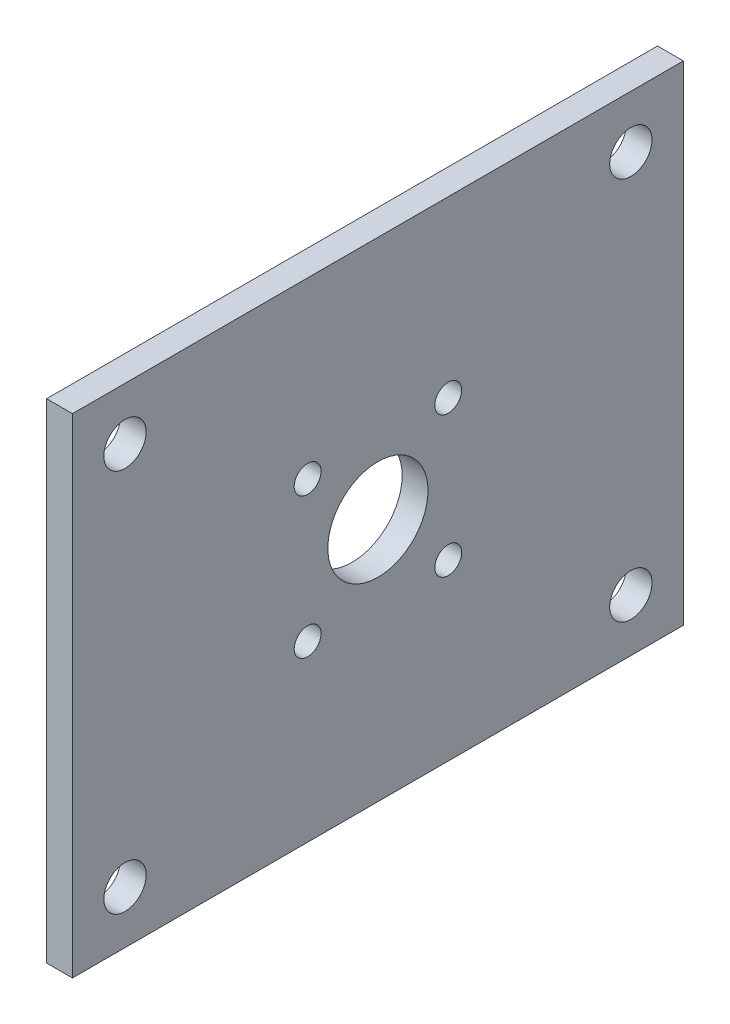
SolidWorks part; units mm, degrees
ref_plane "Front Plane" through (0, 0, 0) normal (0, 0, 1) x (1, 0, 0)
ref_plane "Top Plane" through (0, 0, 0) normal (0, 1, 0) x (1, 0, 0)
ref_plane "Right Plane" through (0, 0, 0) normal (1, 0, 0) x (0, 0, -1)
sketch "Sketch1" plane through (0, 0, 0) normal (1, 0, 0) x (0, 0, -1)
  line L1 (-37.5, -30) -> (37.5, -30)
  line L2 (-37.5, -30) -> (-37.5, 30)
  line L3 (-37.5, 30) -> (37.5, 30)
  line L4 (37.5, -30) -> (37.5, 30)
  line L5 (-37.5, -30) -> (37.5, 30) construction
  line L6 (-37.5, 30) -> (37.5, -30) construction
  point P0 (0, 0)
  dimension "D1" = 75
  dimension "D2" = 60
extrude "Boss-Extrude1" add sketch "Sketch1" along normal blind 1.5875 and the other way blind 1.5875
sketch "Sketch2" plane through (0, 0, 0) normal (1, 0, 0) x (0, 0, -1)
  line L0 (-37.5, 30) -> (-31.05, 30) construction
  line L1 (37.5, 30) -> (-37.5, 30) construction
  line L2 (-31.05, 30) -> (-31.05, 23.55) construction
  line L3 (0, 1.7463) -> (0, -1.7463) construction
  line L4 (1.7463, 0) -> (-1.7463, 0) construction
  circle A0 centre (-31.05, 23.55) radius 2.6
  circle A1 centre (31.05, 23.55) radius 2.6
  circle A2 centre (31.05, -23.55) radius 2.6
  circle A3 centre (-31.05, -23.55) radius 2.6
  dimension "D3" = 5.2
  dimension "D1" = 6.45
  dimension "D2" = 6.45
extrude "Cut-Extrude1" cut sketch "Sketch2" against normal through all both and the other way through all
sketch "Sketch3" plane through (0, 0, 0) normal (1, 0, 0) x (0, 0, -1)
  line L0 (1.7463, 0) -> (-1.7463, 0) construction
  line L5 (-8.63, -8.63) -> (8.63, -8.63) construction
  line L6 (-8.63, -8.63) -> (-8.63, 8.63) construction
  line L7 (-8.63, 8.63) -> (8.63, 8.63) construction
  line L8 (8.63, -8.63) -> (8.63, 8.63) construction
  line L9 (-8.63, -8.63) -> (8.63, 8.63) construction
  line L10 (-8.63, 8.63) -> (8.63, -8.63) construction
  line L11 (0, 1.7463) -> (0, -1.7463) construction
  circle A6 centre (0, 0) radius 6.15
  circle A7 centre (-8.63, 8.63) radius 1.65
  circle A8 centre (-8.63, -8.63) radius 1.65
  circle A9 centre (8.63, -8.63) radius 1.65
  circle A10 centre (8.63, 8.63) radius 1.65
  dimension "D3" = 17.26
  dimension "D1" = 3.3
  dimension "D4" = 12.3
  dimension "D2" = 17.26
extrude "Cut-Extrude2" cut sketch "Sketch3" against normal through all both and the other way through all
